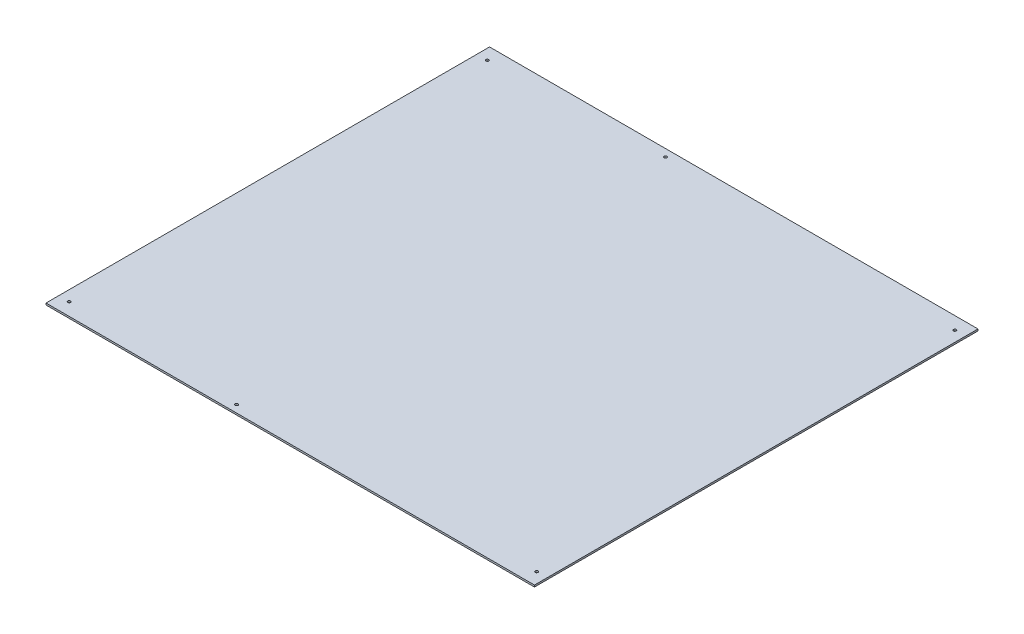
SolidWorks part; units mm, degrees
ref_plane "Alzado" through (0, 0, 0) normal (0, 0, 1) x (1, 0, 0)
ref_plane "Planta" through (0, 0, 0) normal (0, 1, 0) x (1, 0, 0)
ref_plane "Vista lateral" through (0, 0, 0) normal (1, 0, 0) x (0, 0, -1)
sketch "Croquis1" plane through (0, 0, 0) normal (0, 1, 0) x (1, 0, 0)
  line L1 (0, 0) -> (550.5, 0)
  line L2 (0, 0) -> (0, 500)
  line L3 (0, 500) -> (550.5, 500)
  line L4 (550.5, 0) -> (550.5, 500)
  dimension "D1" = 500
  dimension "D2" = 550.5
extrude "Saliente-Extruir1" add sketch "Croquis1" along normal blind 2
sketch "Croquis2" plane through (0, 2, 0) normal (0, 1, 0) x (1, 0, 0)
  line L0 (550.5, 500) -> (0, 500) construction
  line L1 (0, 500) -> (0, 0) construction
  line L2 (275.25, 500) -> (275.25, 0) construction
  line L3 (0, 0) -> (550.5, 0) construction
  line L4 (0, 250) -> (550.5, 250) construction
  line L5 (550.5, 0) -> (550.5, 500) construction
  circle A0 centre (12.5, 485) radius 1.55
  circle A1 centre (538, 485) radius 1.55
  circle A2 centre (538, 15) radius 1.55
  circle A3 centre (12.5, 15) radius 1.55
  dimension "D1" = 3.1
  dimension "D2" = 15
  dimension "D3" = 12.5
extrude "Cortar-Extruir1" cut sketch "Croquis2" against normal up to surface (2 mm away) up to face at (275.25, 0, -250)
sketch "Croquis3" plane through (0, 2, 0) normal (0, 1, 0) x (1, 0, 0)
  line L0 (549.75, 499.25) -> (0.75, 499.25)
  line L1 (0.75, 499.25) -> (0.75, 0.75)
  line L2 (0.75, 0.75) -> (549.75, 0.75)
  line L3 (549.75, 0.75) -> (549.75, 499.25)
  line L4 (0, 500) -> (0, 0)
  line L5 (0, 0) -> (550.5, 0)
  line L6 (550.5, 0) -> (550.5, 500)
  line L7 (550.5, 500) -> (0, 500)
  line L8 (0, 500) -> (0, 0)
  line L9 (0, 0) -> (550.5, 0)
  line L10 (550.5, 0) -> (550.5, 500)
  line L11 (550.5, 500) -> (0, 500)
  dimension "D1" = 0
  dimension "D2" = 0.75
extrude "Cortar-Extruir2" cut sketch "Croquis3" against normal up to surface (2 mm away) up to face at (12.5, 0, -16.55)
sketch "Croquis4" plane through (0, 2, 0) normal (0, 1, 0) x (1, 0, 0)
  line L0 (0.75, 0.75) -> (549.75, 0.75) construction
  line L1 (549.75, 499.25) -> (0.75, 499.25) construction
  line L2 (0.75, 499.25) -> (0.75, 0.75) construction
  circle A0 centre (206.75, 491) radius 1.6
  circle A1 centre (206.75, 9) radius 1.6
  point P8 (112.5434, 491)
  point P9 (332.39, 9)
  point P10 (0, 0)
  point P11 (243.7563, 9)
  point P12 (103.0079, 9)
  point P15 (0, 0)
  dimension "D1" = 3.2
  dimension "D2" = 3.2
  dimension "D3" = 8.25
  dimension "D4" = 8.25
  dimension "D5" = 206
  dimension "D6" = 206
extrude "Cortar-Extruir3" cut sketch "Croquis4" against normal up to surface (2 mm away) up to face at (12.5, 0, -486.55)
